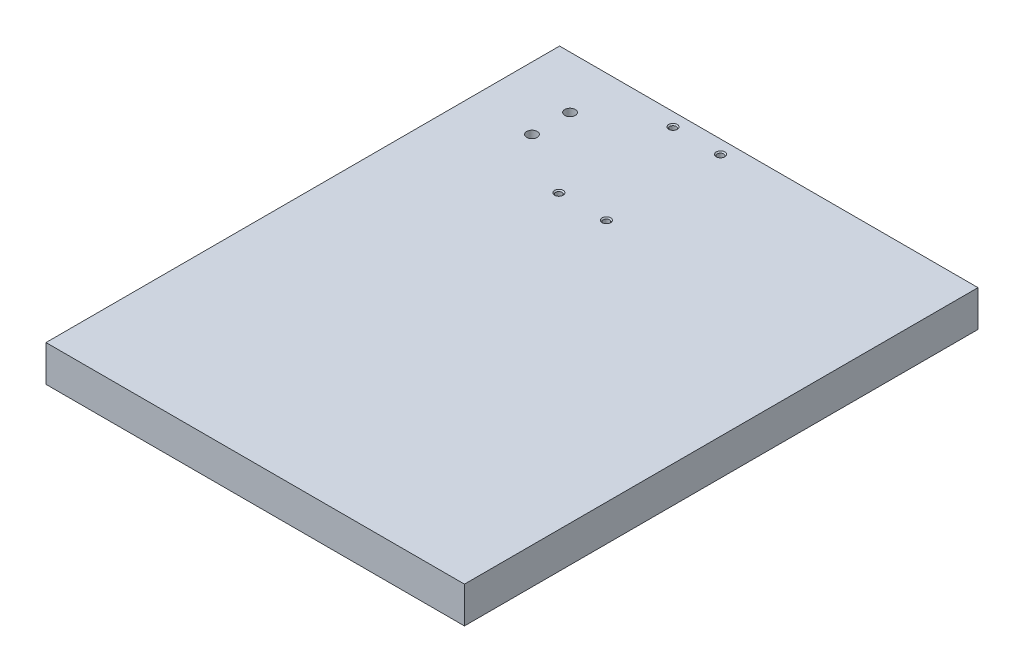
SolidWorks part; units mm, degrees
ref_plane "Front Plane" through (0, 0, 0) normal (0, 0, 1) x (1, 0, 0)
ref_plane "Top Plane" through (0, 0, 0) normal (0, 1, 0) x (1, 0, 0)
ref_plane "Right Plane" through (0, 0, 0) normal (1, 0, 0) x (0, 0, -1)
sketch "Sketch1" plane through (0, 0, 0) normal (0, 1, 0) x (1, 0, 0)
  line L1 (0, 0) -> (220, 0)
  line L2 (0, 0) -> (0, 270)
  line L3 (0, 270) -> (220, 270)
  line L4 (220, 0) -> (220, 270)
  dimension "D1" = 220
  dimension "D2" = 270
extrude "Boss-Extrude1" add sketch "Sketch1" along normal blind 19.05
hole_wizard "M4 Tapped Hole1" positions "Sketch3" profile "Sketch2" tap size "M4" standard "ISO"
sketch "Sketch3" plane through (0, 19.05, 0) normal (0, 1, 0) x (-1, 0, 0)
  line L0 (0, -270) -> (0, 0) construction
  line L1 (-220, -270) -> (0, -270) construction
  point P0 (-66.64, -263)
  point P1 (-91.64, -263)
  point P3 (-91.64, -203)
  point P5 (-66.64, -203)
  dimension "D1" = 66.64
  dimension "D2" = 7
  dimension "D3" = 25
  dimension "D4" = 60
sketch "Sketch2" plane through (66.64, 19.05, -263) normal (1, 0, 0) x (0, 0, 1)
  line L0 (0, 0) -> (0, 75.9914)
  line L1 (0, 75.9914) -> (1.65, 75)
  line L2 (1.65, 75) -> (1.65, 0.6)
  line L3 (1.65, 0.6) -> (2.25, 0)
  line L5 (2.25, 0) -> (0, 0)
  line L6 (-1.65, 0.6) -> (-2.25, 0) construction
  line L10 (0, 75.9914) -> (-1.65, 75) construction
  line L11 (0, -6.35) -> (0, 107.95) construction
  dimension "Tap Drill Dia." = 3.3
  dimension "Tap Drill Depth" = 75
  dimension "Near C'Sink Dia." = 4.5
  dimension "Near C'Sink Angle" = 90
  dimension "Drill Angle" = 118
cosmetic thread "Hole Thread1" parameters "D1"=8, "D2"=4
cosmetic thread "Hole Thread2" parameters "D1"=8, "D2"=4
cosmetic thread "Hole Thread3" parameters "D1"=8, "D2"=4
cosmetic thread "Hole Thread4" parameters "D1"=8, "D2"=4
hole_wizard "CBORE for M5 Hex Socket Head Cap Screw1" positions "Sketch5" profile "Sketch6" counterbore size "M5" standard "ISO" end condition through all
sketch "Sketch5" plane through (0, 0, 0) normal (0, -1, 0) x (1, 0, 0)
  line L0 (220, -270) -> (0, -270) construction
  line L1 (0, -270) -> (0, 0) construction
  point P0 (33, -242.5)
  point P1 (33, -222.5)
  dimension "D1" = 27.5
  dimension "D2" = 33
  dimension "D3" = 20
sketch "Sketch6" plane through (33, 0, -242.5) normal (1, 0, 0) x (0, 0, -1)
  line L0 (0, 0) -> (0, 19.05)
  line L1 (0, 19.05) -> (2.75, 19.05)
  line L3 (2.75, 19.05) -> (2.75, 5)
  line L4 (2.75, 5) -> (5, 5)
  line L5 (5, 5) -> (5, 0)
  line L7 (5, 0) -> (0, 0)
  line L11 (0, -6.35) -> (0, 107.95) construction
  dimension "Thru Hole Dia." = 5.5
  dimension "Thru Hole Depth" = 19.05
  dimension "C'Bore Dia." = 10
  dimension "C'Bore Depth" = 5
